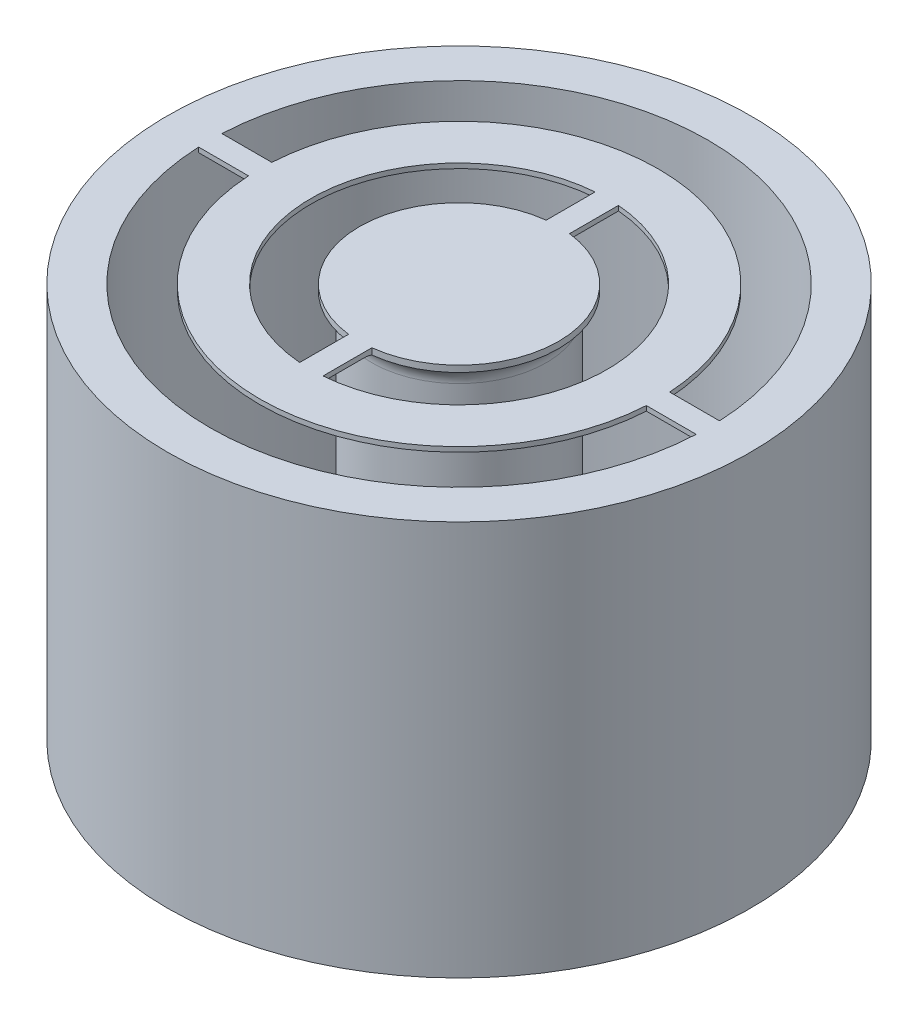
SolidWorks part; units mm, degrees
ref_plane "Front Plane" through (0, 0, 0) normal (0, 0, 1) x (1, 0, 0)
ref_plane "Top Plane" through (0, 0, 0) normal (0, 1, 0) x (1, 0, 0)
ref_plane "Right Plane" through (0, 0, 0) normal (1, 0, 0) x (0, 0, -1)
sketch "Sketch1" plane through (0, 0, 0) normal (0, 1, 0) x (1, 0, 0)
  line L0 (0, 0.6) -> (14.988, 0.6) construction
  line L1 (-12.8017, 0.6) -> (-10.2352, 0.6)
  line L2 (14.988, 0.6) -> (-14.988, 0.6) construction
  line L3 (10.2352, 0.6) -> (12.8017, 0.6)
  line L4 (-15, 0) -> (15, 0) construction
  line L5 (0.6, 0) -> (0.6, 14.988) construction
  line L6 (-0.6, 0) -> (-0.6, 14.988) construction
  line L7 (-0.6, 7.6002) -> (-0.6, 5.085)
  line L8 (0.6, 5.085) -> (0.6, 7.6002)
  line L9 (0.6, -5.085) -> (0.6, -7.6002)
  line L10 (-0.6, -7.6002) -> (-0.6, -5.085)
  line L11 (-12.8017, -0.6) -> (-10.2352, -0.6)
  line L12 (10.2352, -0.6) -> (12.8017, -0.6)
  circle A0 centre (0, 0) radius 15
  arc A6 (-12.8017, 0.6) -> (12.8017, 0.6) centre (0, 0) cw
  arc A7 (-10.2352, 0.6) -> (10.2352, 0.6) centre (0, 0) cw
  arc A8 (-0.6, 7.6002) -> (-0.6, -7.6002) centre (0, 0) ccw
  arc A9 (0.6, 7.6002) -> (0.6, -7.6002) centre (0, 0) cw
  arc A10 (-0.6, 5.085) -> (-0.6, -5.085) centre (0, 0) ccw
  arc A11 (0.6, 5.085) -> (0.6, -5.085) centre (0, 0) cw
  arc A12 (-10.2352, -0.6) -> (10.2352, -0.6) centre (0, 0) ccw
  arc A13 (-12.8017, -0.6) -> (12.8017, -0.6) centre (0, 0) ccw
extrude "Boss-Extrude1" add sketch "Sketch1" along normal blind 0.25
sketch "Sketch2" plane through (0, 0.25, 0) normal (0, 1, 0) x (1, 0, 0)
  circle A0 centre (0, 0) radius 15
  circle A1 centre (0, 0) radius 12.8157
extrude "Boss-Extrude2" add sketch "Sketch2" against normal blind 20.32
sketch "Sketch3" plane through (0, 0, 0) normal (0, -1, 0) x (1, 0, 0)
  line L4 (4.4901, 0) -> (-4.4901, 0) construction
  line L5 (0, -4.4901) -> (0, 4.4901) construction
  line L6 (12.8017, 0.6) -> (10.2352, 0.6) construction
  line L8 (-1.524, 2.667) -> (1.524, 2.667)
  line L9 (-1.524, 2.667) -> (-1.524, -2.667)
  line L10 (-1.524, -2.667) -> (1.524, -2.667)
  line L11 (1.524, 2.667) -> (1.524, -2.667)
  line L12 (-1.524, 2.667) -> (1.524, -2.667) construction
  line L13 (-1.524, -2.667) -> (1.524, 2.667) construction
  line L14 (-2.667, 1.524) -> (2.667, 1.524)
  line L15 (-2.667, 1.524) -> (-2.667, -1.524)
  line L16 (-2.667, -1.524) -> (2.667, -1.524)
  line L17 (2.667, 1.524) -> (2.667, -1.524)
  line L18 (-2.667, 1.524) -> (2.667, -1.524) construction
  line L19 (-2.667, -1.524) -> (2.667, 1.524) construction
  circle A0 centre (0, 0) radius 4.4901
  point P1 (0, 0)
  point P3 (0, 0)
  point P13 (0, 0)
  dimension "D1" = 6.35
  dimension "D2" = 6.35
  dimension "D3" = 0
  dimension "D4" = 3.048
  dimension "D5" = 5.334
  dimension "D6" = 3.048
  dimension "D7" = 5.334
extrude "Boss-Extrude3" add sketch "Sketch3" along normal blind 19.05
fillet "Fillet2" radius 1.016 1 edges at (0, 0, 4.4901)
